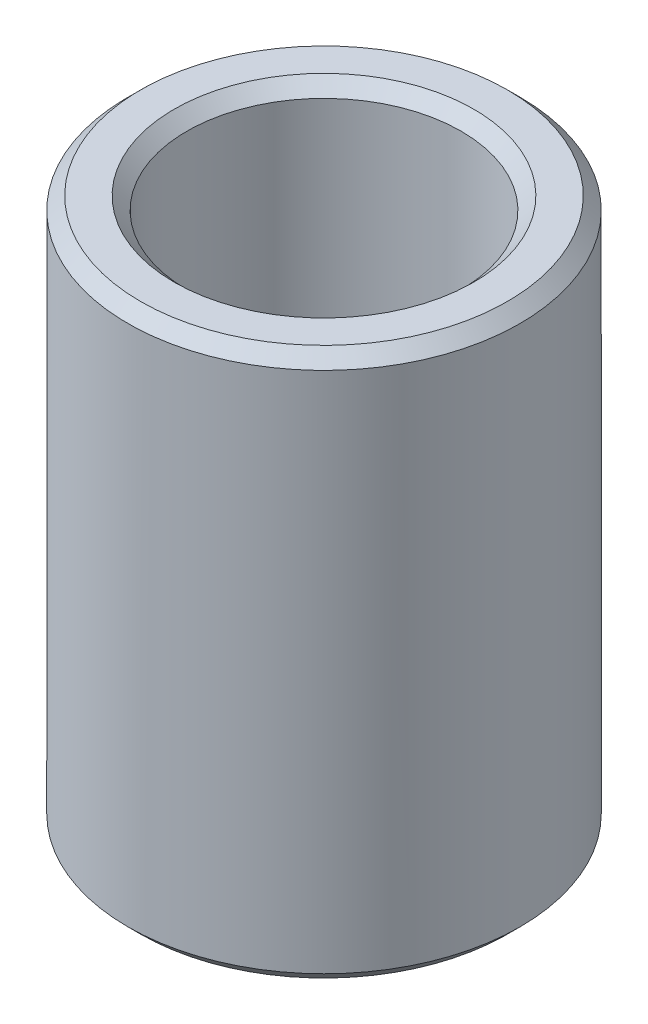
SolidWorks part; units mm, degrees
ref_plane "Front Plane" through (0, 0, 0) normal (0, 0, 1) x (1, 0, 0)
ref_plane "Top Plane" through (0, 0, 0) normal (0, 1, 0) x (1, 0, 0)
ref_plane "Right Plane" through (0, 0, 0) normal (1, 0, 0) x (0, 0, -1)
sketch "Sketch1" plane through (0, 0, 0) normal (0, 1, 0) x (1, 0, 0)
  circle A0 centre (0, 0) radius 42.5
  dimension "SLEEVE_OD" = 85
extrude "Boss-Extrude1" add sketch "Sketch1" along normal blind 118.7773
sketch "Sketch2" plane through (0, 0, 0) normal (0, 1, 0) x (1, 0, 0)
  circle A0 centre (0, 0) radius 29.7294
  dimension "BORE_D" = 59.4588
extrude "Cut-Extrude1" cut sketch "Sketch2" along normal through all
chamfer "Chamfer1" distance 2.7529 angle 45 4 edges at (0, 118.7773, 29.7294) (0, 0, 29.7294) (0, 0, 42.5) (0, 118.7773, 42.5)
